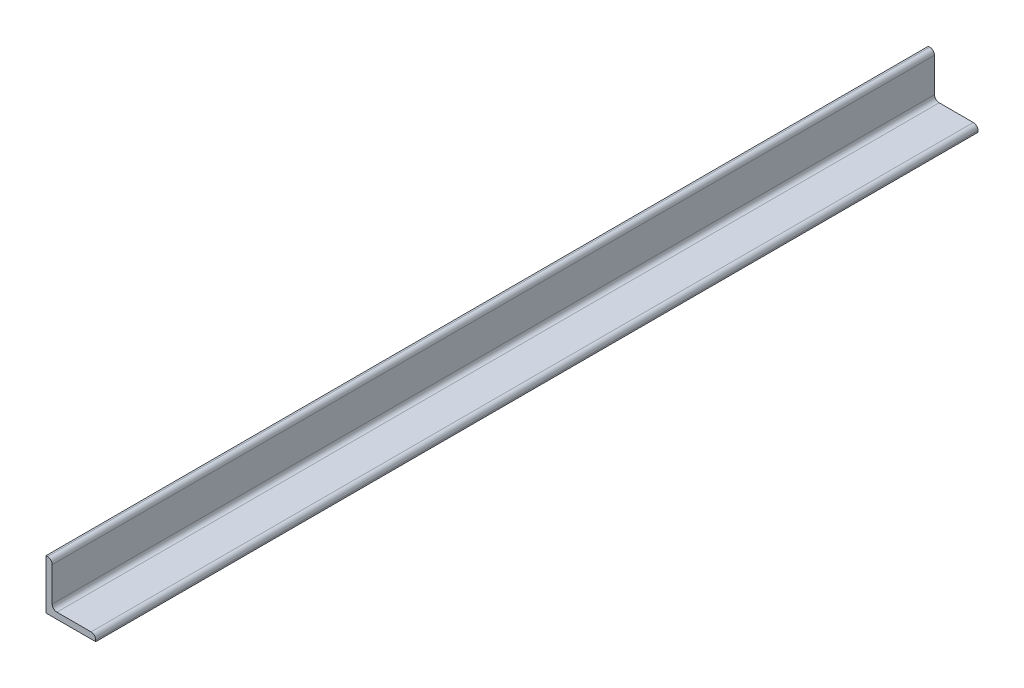
SolidWorks part; units mm, degrees
ref_plane "Front Plane" through (0, 0, 0) normal (0, 0, 1) x (1, 0, 0)
ref_plane "Top Plane" through (0, 0, 0) normal (0, 1, 0) x (1, 0, 0)
ref_plane "Right Plane" through (0, 0, 0) normal (1, 0, 0) x (0, 0, -1)
sketch "Sketch1" plane through (0, 0, 0) normal (0, 0, 1) x (1, 0, 0)
  line L0 (0, 0) -> (0, 50.8)
  line L1 (0, 50.8) -> (1.5926, 50.8)
  line L2 (6.35, 46.0426) -> (6.35, 11.1125)
  line L3 (11.1125, 6.35) -> (46.0426, 6.35)
  line L4 (50.8, 1.5926) -> (50.8, 0)
  line L5 (50.8, 0) -> (0, 0)
  arc A0 (50.8, 1.5926) -> (46.0426, 6.35) centre (46.0426, 1.5926) ccw
  arc A1 (1.5926, 50.8) -> (6.35, 46.0426) centre (1.5926, 46.0426) cw
  arc A2 (11.1125, 6.35) -> (6.35, 11.1125) centre (11.1125, 11.1125) cw
  circle A3 centre (0, 0) radius 4.7625 construction
  dimension "D2" = 1.5926
  dimension "Radius_1" = 4.7625
  dimension "Radius_2" = 4.7625
  dimension "D1" = 6.35
  dimension "V_leg" = 50.8
  dimension "H_leg" = 50.8
  dimension "Thickness" = 6.35
  dimension "Flat_wid" = 1.5926
extrude "Boss-Extrude1" add sketch "Sketch1" along normal mid plane 901.7
